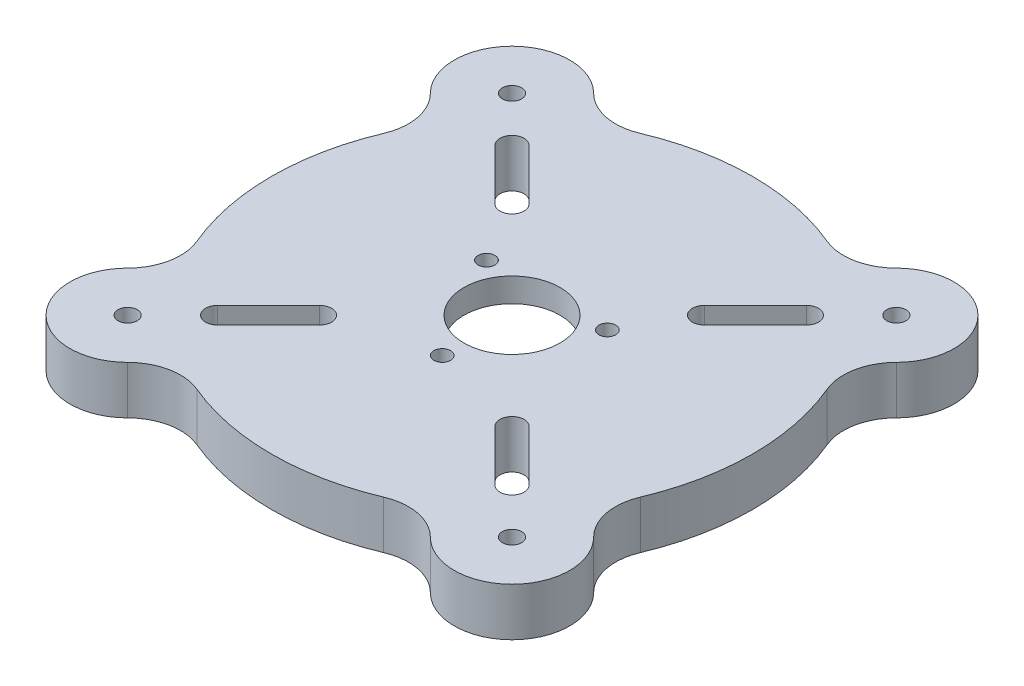
SolidWorks part; units mm, degrees
ref_plane "Płaszczyzna przednia" through (0, 0, 0) normal (0, 0, 1) x (1, 0, 0)
ref_plane "Płaszczyzna górna" through (0, 0, 0) normal (0, 1, 0) x (1, 0, 0)
ref_plane "Płaszczyzna prawa" through (0, 0, 0) normal (1, 0, 0) x (0, 0, -1)
sketch "Szkic1" plane through (0, 0, 0) normal (0, 1, 0) x (1, 0, 0)
  line L0 (-39.9515, -39.9515) -> (39.9515, 39.9515) construction
  line L1 (-48.4368, -31.4663) -> (31.4663, 48.4368) construction
  line L2 (-31.4663, -48.4368) -> (48.4368, 31.4663) construction
  line L3 (0, 0) -> (0, 50) construction
  line L4 (39.9515, -39.9515) -> (-39.9515, 39.9515) construction
  line L5 (48.4368, -31.4663) -> (-31.4663, 48.4368) construction
  line L6 (31.4663, -48.4368) -> (-48.4368, 31.4663) construction
  line L7 (20, 20) -> (30.6066, 30.6066) construction
  line L8 (18.2322, 21.7678) -> (28.8388, 32.3744)
  line L9 (21.7678, 18.2322) -> (32.3744, 28.8388)
  line L10 (20, -20) -> (30.6066, -30.6066) construction
  line L11 (21.7678, -18.2322) -> (32.3744, -28.8388)
  line L12 (18.2322, -21.7678) -> (28.8388, -32.3744)
  line L13 (-20, -20) -> (-30.6066, -30.6066) construction
  line L14 (-18.2322, -21.7678) -> (-28.8388, -32.3744)
  line L15 (-21.7678, -18.2322) -> (-32.3744, -28.8388)
  line L16 (-20, 20) -> (-30.6066, 30.6066) construction
  line L17 (-21.7678, 18.2322) -> (-32.3744, 28.8388)
  line L18 (-18.2322, 21.7678) -> (-28.8388, 32.3744)
  circle A0 centre (0, 0) radius 50
  arc A1 (-48.4368, -31.4663) -> (-31.4663, -48.4368) centre (-39.9515, -39.9515) ccw construction
  arc A2 (48.4368, 31.4663) -> (31.4663, 48.4368) centre (39.9515, 39.9515) ccw construction
  arc A3 (48.4368, -31.4663) -> (31.4663, -48.4368) centre (39.9515, -39.9515) cw construction
  arc A4 (-48.4368, 31.4663) -> (-31.4663, 48.4368) centre (-39.9515, 39.9515) cw construction
  arc A5 (19.4135, 46.0773) -> (31.4663, 48.4368) centre (23.6858, 56.2173) ccw
  arc A6 (48.4368, 31.4663) -> (46.0773, 19.4135) centre (56.2173, 23.6858) ccw
  arc A7 (18.2322, 21.7678) -> (21.7678, 18.2322) centre (20, 20) ccw
  arc A8 (32.3744, 28.8388) -> (28.8388, 32.3744) centre (30.6066, 30.6066) ccw
  circle A9 centre (39.9515, 39.9515) radius 2
  arc A10 (48.4368, 31.4663) -> (31.4663, 48.4368) centre (39.9515, 39.9515) ccw
  arc A11 (31.4663, -48.4368) -> (48.4368, -31.4663) centre (39.9515, -39.9515) ccw
  arc A12 (46.0773, -19.4135) -> (48.4368, -31.4663) centre (56.2173, -23.6858) ccw
  arc A13 (31.4663, -48.4368) -> (19.4135, -46.0773) centre (23.6858, -56.2173) ccw
  circle A14 centre (39.9515, -39.9515) radius 2
  arc A15 (21.7678, -18.2322) -> (18.2322, -21.7678) centre (20, -20) ccw
  arc A16 (28.8388, -32.3744) -> (32.3744, -28.8388) centre (30.6066, -30.6066) ccw
  arc A17 (-48.4368, -31.4663) -> (-31.4663, -48.4368) centre (-39.9515, -39.9515) ccw
  arc A18 (-19.4135, -46.0773) -> (-31.4663, -48.4368) centre (-23.6858, -56.2173) ccw
  arc A19 (-48.4368, -31.4663) -> (-46.0773, -19.4135) centre (-56.2173, -23.6858) ccw
  circle A20 centre (-39.9515, -39.9515) radius 2
  arc A21 (-18.2322, -21.7678) -> (-21.7678, -18.2322) centre (-20, -20) ccw
  arc A22 (-32.3744, -28.8388) -> (-28.8388, -32.3744) centre (-30.6066, -30.6066) ccw
  arc A23 (-31.4663, 48.4368) -> (-48.4368, 31.4663) centre (-39.9515, 39.9515) ccw
  arc A24 (-46.0773, 19.4135) -> (-48.4368, 31.4663) centre (-56.2173, 23.6858) ccw
  arc A25 (-31.4663, 48.4368) -> (-19.4135, 46.0773) centre (-23.6858, 56.2173) ccw
  circle A26 centre (-39.9515, 39.9515) radius 2
  arc A27 (-21.7678, 18.2322) -> (-18.2322, 21.7678) centre (-20, 20) ccw
  arc A28 (-28.8388, 32.3744) -> (-32.3744, 28.8388) centre (-30.6066, 30.6066) ccw
  point P5 (0, 0)
  point P13 (0, 0)
  point P26 (25.3033, 25.3033)
  point P45 (25.3033, -25.3033)
  point P61 (-25.3033, -25.3033)
  point P77 (-25.3033, 25.3033)
  point P85 (0, 0)
  dimension "D1" = 100
  dimension "D2" = 12
  dimension "D4" = 2.5
  dimension "D8" = 4
  dimension "D9" = 4
  dimension "D3" = 113
  dimension "D5" = 15
  dimension "D6" = 45
  dimension "D7" = 20
extrude "Dodanie-wyciągnięcie1" add sketch "Szkic1" along normal blind 10 contours A0 A28 L18 A27 L17 A22 L15 A21 L14 A16 L12 A15 L11 A8 L9 A7 L8 | A19 A17 A18 A0 A20 | A25 A23 A24 A0 A26 | A6 A10 A5 A0 A9 | A13 A11 A12 A0 A14 region at (0, 0, 0) region at (35.6807, 0, -35.6807) region at (44.9674, 0, 25.8881) region at (-35.6807, 0, -35.6807) region at (-25.8881, 0, 44.9674)
sketch "Szkic2" plane through (0, 0, 0) normal (0, -1, 0) x (1, 0, 0)
  circle A0 centre (0, 0) radius 21.25
  circle A1 centre (0, 14.5) radius 1.75
  circle A2 centre (12.5589, -7.2491) radius 1.75
  circle A3 centre (-12.5559, -7.2509) radius 1.75
  circle A4 centre (0, 0) radius 10
  point P11 (0.001, 0)
  dimension "D1" = 42.5
  dimension "D3" = 3.5
  dimension "D6" = 20
  dimension "D2" = 14.5
  dimension "D4" = 3
  dimension "D5" = 19.8185
extrude "Wytnij-wyciągnięcie3" cut sketch "Szkic2" against normal blind 5
extrude "Wytnij-wyciągnięcie6" cut sketch "Szkic2<8>" against normal through all contours A3 | A1 | A2 | A4
sketch "Szkic2<8>" plane through (0, 0, 0) normal (0, -1, 0) x (1, 0, 0) same geometry as "Szkic2"
